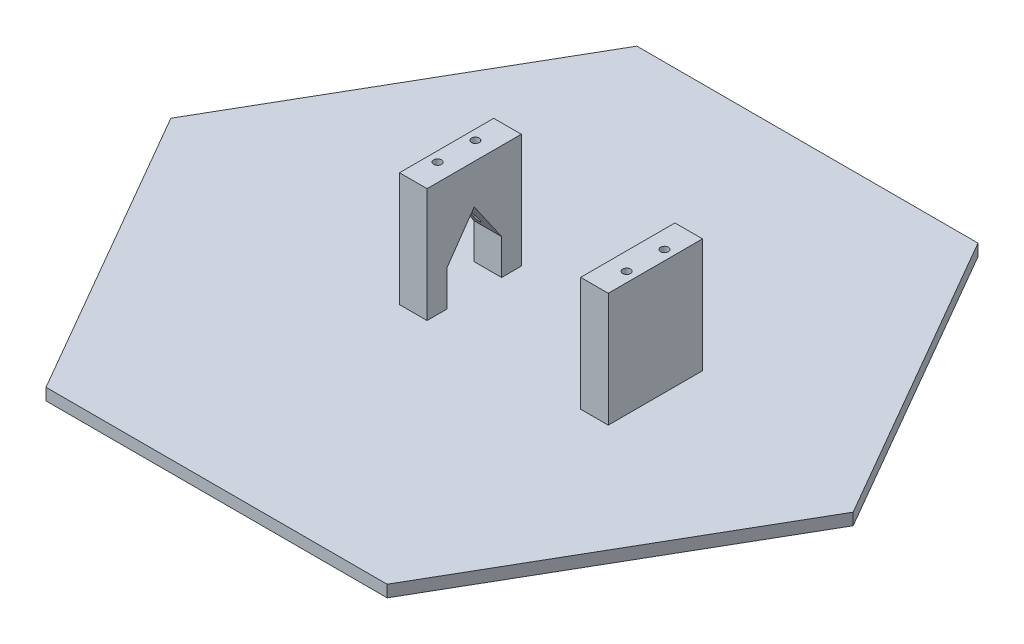
SolidWorks part; units mm, degrees
ref_plane "Front Plane" through (0, 0, 0) normal (0, 0, 1) x (1, 0, 0)
ref_plane "Top Plane" through (0, 0, 0) normal (0, 1, 0) x (1, 0, 0)
ref_plane "Right Plane" through (0, 0, 0) normal (1, 0, 0) x (0, 0, -1)
sketch "Sketch1" plane through (0, 0, 0) normal (0, 1, 0) x (1, 0, 0)
  line L1 (86.6025, 0) -> (43.3013, 75)
  line L2 (43.3013, 75) -> (-43.3013, 75)
  line L3 (-43.3013, 75) -> (-86.6025, 0)
  line L4 (-86.6025, 0) -> (-43.3013, -75)
  line L5 (-43.3013, -75) -> (43.3013, -75)
  line L6 (43.3013, -75) -> (86.6025, 0)
  circle A0 centre (0, 0) radius 75 construction
  dimension "D1" = 150
extrude "Boss-Extrude1" add sketch "Sketch1" along normal blind 3
sketch "Sketch2" plane through (0, 3, 0) normal (0, 1, 0) x (1, 0, 0)
  line L0 (9.9, 11.9602) -> (9.9, -11.9602) construction
  line L5 (-16.6, -11.9602) -> (36.4, -11.9602) construction
  line L6 (-16.6, -11.9602) -> (-16.6, 11.9602) construction
  line L7 (-16.6, 11.9602) -> (36.4, 11.9602) construction
  line L8 (36.4, -11.9602) -> (36.4, 11.9602)
  line L9 (-16.6, 0) -> (36.4, 0) construction
  line L10 (-9.6, 11.9602) -> (-9.6, -11.9602) construction
  line L11 (29.4, 11.9602) -> (29.4, -11.9602)
  line L12 (-16.6, 6.9602) -> (-9.6, 6.9602)
  line L13 (-16.6, -6.9602) -> (-9.6, -6.9602)
  line L14 (29.4, 11.9602) -> (36.4, 11.9602)
  line L15 (29.4, -11.9602) -> (36.4, -11.9602)
  line L16 (-9.6, -11.9602) -> (-16.6, -11.9602)
  line L17 (-16.6, -11.9602) -> (-16.6, -6.9602)
  line L18 (-9.6, -6.9602) -> (-9.6, -11.9602)
  line L19 (-16.6, 6.9602) -> (-16.6, 11.9602)
  line L20 (-16.6, 11.9602) -> (-9.6, 11.9602)
  line L21 (-9.6, 11.9602) -> (-9.6, 6.9602)
  circle A0 centre (-14.1, 4.8) radius 1 construction
  circle A1 centre (-14.1, -4.8) radius 1 construction
  circle A2 centre (33.9, -4.8) radius 1
  circle A3 centre (33.9, 4.8) radius 1
  circle A4 centre (0, 0) radius 4.1718 construction
  circle A5 centre (-14.1, -4.8) radius 1
  circle A6 centre (-14.1, 4.8) radius 1
  point P10 (-9.6, 11.9602)
  point P14 (-9.6, 0)
  point P22 (-16.6, 6.9602)
  dimension "D2" = 4.8
  dimension "D3" = 2.5
  dimension "D5" = 2
  dimension "D1" = 53
  dimension "D4" = 7
  dimension "D6" = 5
  dimension "D7" = 9.6
extrude "Boss-Extrude4" add sketch "Sketch2" along normal blind 29
sketch "Sketch4" plane through (-16.6, 0, 0) normal (-1, 0, 0) x (0, 0, 1)
  line L0 (0, 3) -> (0, 32) construction
  line L1 (-11.9602, 3) -> (11.9602, 3) construction
  line L2 (-11.9602, 32) -> (11.9602, 32) construction
  line L3 (-6.9602, 32) -> (-6.9602, 3) construction
  line L4 (-6.9602, 12) -> (0, 22)
  line L5 (0, 22) -> (0, 32)
  line L6 (6.9602, 32) -> (-6.9602, 32)
  line L7 (-6.9602, 32) -> (-6.9602, 12)
  line L8 (6.9602, 12) -> (0, 22)
  line L9 (6.9602, 32) -> (6.9602, 12)
  point P6 (-6.9602, 12)
  point P7 (0, 22)
  dimension "D1" = 9
  dimension "D2" = 10
extrude "Boss-Extrude5" add sketch "Sketch4" against normal up to surface (7 mm away) contours L8 L9 L6 L7 L4 up to face at (-9.6, 17.5, -9.4602)
extrude "Cut-Extrude1" cut sketch "Sketch2<4>" along normal up to surface (29 mm away) contours A5 | A6 up to face at (-13.1, 32, 0)
sketch "Sketch2<4>" plane through (0, 3, 0) normal (0, 1, 0) x (1, 0, 0) same geometry as "Sketch2"
